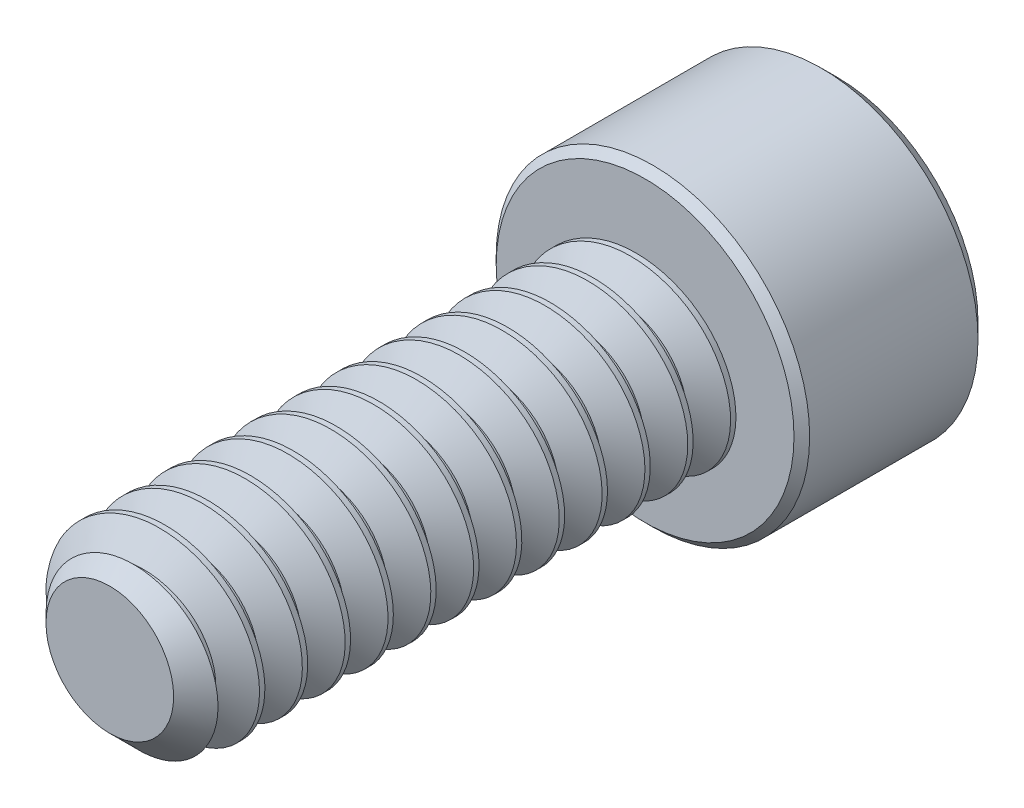
SolidWorks part; units mm, degrees
ref_plane "Front Plane" through (0, 0, 0) normal (0, 0, 1) x (1, 0, 0)
ref_plane "Top Plane" through (0, 0, 0) normal (0, 1, 0) x (1, 0, 0)
ref_plane "Right Plane" through (0, 0, 0) normal (1, 0, 0) x (0, 0, -1)
sketch "Sketch0" plane through (0, 0, 0) normal (1, 0, 0) x (0, 0, -1)
  line L0 (0, 0) -> (7.9375, 0) construction
  point P2 (10.7823, 0)
  point P4 (0, 0)
  dimension "D1" = 7.9375
  dimension "D2" = 2.8448
  dimension "Min Thread" = 0
sketch "Sketch1" plane through (0, 0, 0) normal (0, 0, 1) x (1, 0, 0)
  circle A0 centre (0, 0) radius 1.4224
  dimension "OD" = 2.8448
extrude "Extrude1" add sketch "Sketch1" against normal blind 7.9375
sketch "Sketch2" plane through (0, 0, 0) normal (0, 0, 1) x (1, 0, 0)
  circle A0 centre (0, 0) radius 1.4224 construction
  circle A1 centre (0, 0) radius 1.4224
curve "Helix/Spiral1" pitch 0.635 height 8.5725 radius 1.4224 centre (0, 0, 0) axis (0, 0, -1) start towards (0, 1, 0) parameters "pitch"=0.635
chamfer "Chamfer3" distance 0.4763 angle 45 1 edges at (1.4224, 0, 0)
sketch "Sketch3" plane through (0, 0, 0) normal (1, 0, 0) x (0, 0, -1)
  line L0 (-0.5556, 1.4224) -> (-0.3175, 1.01)
  line L1 (-0.3175, 1.01) -> (-0.2381, 1.01)
  line L2 (-0.2381, 1.01) -> (0, 1.4224)
  line L3 (-0.5556, 1.4224) -> (0, 1.4224)
  line L4 (-0.2778, 1.4224) -> (-0.2778, 1.01) construction
  line L5 (-0.4366, 1.2162) -> (-0.1191, 1.2162) construction
  line L6 (0, 1.4224) -> (0, -1.4224) construction
  dimension "D1" = 0.0794
  dimension "D2" = 0.3175
  dimension "D3" = 60
sweep "Cut-Sweep1" cut profiles "Sketch3" path "Helix/Spiral1" align with end faces yes
sketch "Sketch5" plane through (0, 0, 0) normal (1, 0, 0) x (0, 0, -1)
  line L0 (7.9375, -1.0149) -> (7.9375, 1.0232) construction
  line L1 (7.9375, 1.4224) -> (0, 1.4224)
  line L2 (7.9375, 1.4224) -> (7.9375, 0)
  line L3 (7.9375, 0) -> (-0.5177, 0)
  line L4 (0, 0) -> (7.9375, 0) construction
  line L5 (0, 1.4224) -> (-0.5177, 0)
  line L6 (0, 0) -> (10.4775, 0) construction
  dimension "D1" = 70
  dimension "D3" = 2.54
revolve "partially thread" [suppressed] add sketch "Sketch5" angle 360 about L6
sketch "Sketch6" plane through (0, 0, -7.9375) normal (0, 0, -1) x (-1, 0, 0)
  circle A0 centre (0, 0) radius 2.3241
  dimension "head dia" = 4.6482
extrude "Extrude2" add sketch "Sketch6" along normal blind 2.8448
sketch "Sketch7" plane through (0, 0, -10.7823) normal (0, 0, -1) x (-1, 0, 0)
  line L1 (0, 1.3748) -> (-1.1906, 0.6874)
  line L2 (-1.1906, 0.6874) -> (-1.1906, -0.6874)
  line L3 (-1.1906, -0.6874) -> (0, -1.3748)
  line L4 (0, -1.3748) -> (1.1906, -0.6874)
  line L5 (1.1906, -0.6874) -> (1.1906, 0.6874)
  line L6 (1.1906, 0.6874) -> (0, 1.3748)
  circle A0 centre (0, 0) radius 1.1906 construction
  dimension "hex dia" = 2.3813
extrude "Cut-Extrude1" cut sketch "Sketch7" against normal blind 1.7859
sketch "Sketch8" plane through (0, 0, -10.7823) normal (0, 0, -1) x (-1, 0, 0)
  circle A0 centre (0, 0) radius 1.3748
extrude "Cut-Extrude2" cut sketch "Sketch8" against normal through all draft 45
chamfer "Chamfer1" distance 0.2324 angle 45 1 edges at (-2.3241, 0, -10.7823)
chamfer "Chamfer2" distance 0.1162 angle 45 1 edges at (-2.3241, 0, -7.9375)
sketch "Sketch9" plane through (0, 0, 0) normal (1, 0, 0) x (0, 0, -1)
  line L0 (0, 1.4224) -> (0, -1.4224) construction
  line L1 (1.5875, 1.4224) -> (1.5875, -1.4224) construction
  line L2 (10.7823, 2.3241) -> (10.7823, -2.3241) construction
  line L3 (7.9375, 2.3241) -> (7.9375, -2.3241) construction
  line L4 (7.9375, 2.2079) -> (7.9375, -2.2079) construction
  line L5 (10.7823, -2.0917) -> (10.7823, 2.0917) construction
  line L6 (7.9375, -2.3241) -> (7.9375, 2.3241) construction
  line L7 (0, 0.9462) -> (0, -0.9462) construction
  line L8 (-0.5556, 1.4224) -> (0, 1.4224) construction
  line L9 (1.5875, 0) -> (0, 0) construction
  dimension "D1" = 1.5875
equation "\"D3@Helix/Spiral1\" = \"screw length@Extrude1\"+\"pitch@Helix/Spiral1\""
equation "\"D1@Sketch3\" = \"pitch@Helix/Spiral1\"*.125"
equation "\"D2@Sketch3\" = \"pitch@Helix/Spiral1\"*.5"
equation "\"D1@Cut-Extrude1\" = \"hex dia@Sketch7\"*.75"
equation "\"D1@Chamfer1\" = \"head dia@Sketch6\"*.05"
equation "\"D1@Sketch9\" = \"pitch@Helix/Spiral1\"*2.50"
equation "\"D1@Chamfer2\" = \"D1@Chamfer1\"/2"
equation "\"D1@Chamfer3\" = \"pitch@Helix/Spiral1\"*.750"
equation "\"D1@Sketch0\" = \"screw length@Extrude1\""
equation "\"D2@Sketch0\" = \"head depth@Extrude2\""
